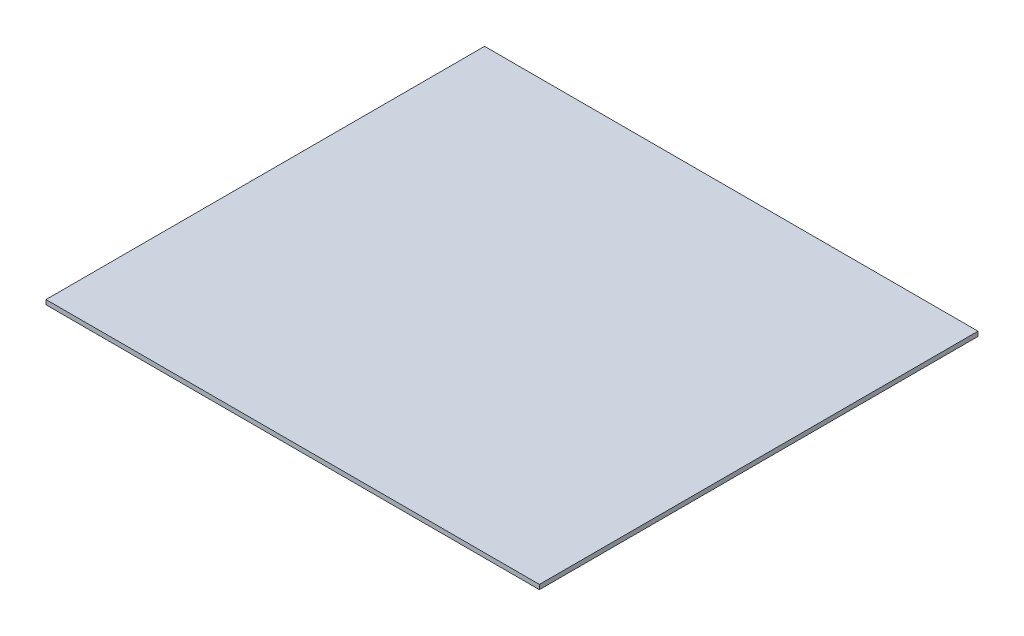
SolidWorks part; units mm, degrees
material "Pine"
ref_plane "Front Plane" through (0, 0, 0) normal (0, 0, 1) x (1, 0, 0)
ref_plane "Top Plane" through (0, 0, 0) normal (0, 1, 0) x (1, 0, 0)
ref_plane "Right Plane" through (0, 0, 0) normal (1, 0, 0) x (0, 0, -1)
sketch "Sketch1" plane through (0, 0, 0) normal (0, 1, 0) x (1, 0, 0)
  line L1 (-287.2212, -374.6626) -> (398.5788, -374.6626)
  line L2 (-287.2212, -374.6626) -> (-287.2212, 234.9374)
  line L3 (-287.2212, 234.9374) -> (398.5788, 234.9374)
  line L4 (398.5788, -374.6626) -> (398.5788, 234.9374)
  dimension "D1" = 685.8
  dimension "D2" = 609.6
extrude "Boss-Extrude1" add sketch "Sketch1" along normal blind 6.35 contours L2 L3 L4 L1
